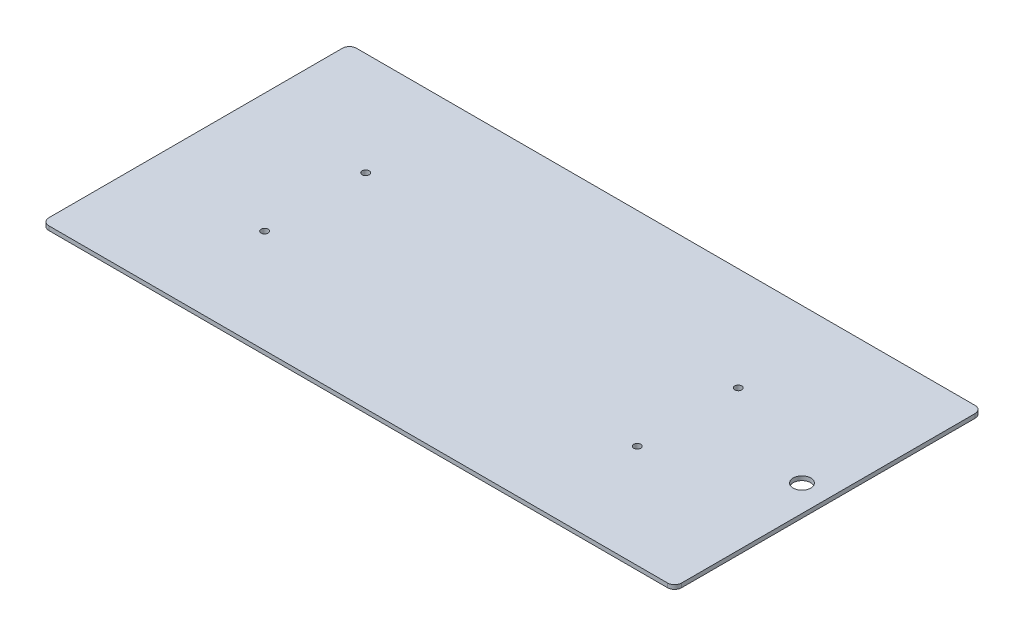
SolidWorks part; units mm, degrees
material "ABS"
ref_plane "Front Plane" through (0, 0, 0) normal (0, 0, 1) x (1, 0, 0)
ref_plane "Top Plane" through (0, 0, 0) normal (0, 1, 0) x (1, 0, 0)
ref_plane "Right Plane" through (0, 0, 0) normal (1, 0, 0) x (0, 0, -1)
sketch "Sketch1" plane through (0, 0, 0) normal (0, 1, 0) x (1, 0, 0)
  line L0 (-303.5027, 0) -> (303.5027, 0) construction
  line L1 (-223.52, -111.125) -> (223.52, -111.125)
  line L2 (-228.6, -106.045) -> (-228.6, 106.045)
  line L3 (-223.52, 111.125) -> (223.52, 111.125)
  line L4 (228.6, -106.045) -> (228.6, 106.045)
  line L5 (-228.6, -111.125) -> (228.6, 111.125) construction
  line L6 (-228.6, 111.125) -> (228.6, -111.125) construction
  line L7 (-303.5027, 36.5125) -> (303.5027, 36.5125) construction
  line L8 (-303.5027, -36.5125) -> (303.5027, -36.5125) construction
  line L9 (127, 111.125) -> (127, -111.125) construction
  line L10 (-142.24, 111.125) -> (-142.24, -111.125) construction
  arc A0 (223.52, 111.125) -> (228.6, 106.045) centre (223.52, 106.045) cw
  arc A1 (223.52, -111.125) -> (228.6, -106.045) centre (223.52, -106.045) ccw
  arc A2 (-223.52, -111.125) -> (-228.6, -106.045) centre (-223.52, -106.045) cw
  arc A3 (-228.6, 106.045) -> (-223.52, 111.125) centre (-223.52, 106.045) cw
  circle A4 centre (127, 36.5125) radius 2.54
  circle A5 centre (127, -36.5125) radius 2.54
  circle A6 centre (-142.24, 36.5125) radius 2.54
  circle A7 centre (-142.24, -36.5125) radius 2.54
  circle A8 centre (209.55, 0) radius 6.35
  point P0 (0, 0)
  point P20 (0, 0)
  point P37 (228.6, 0)
  dimension "D3" = 5.08
  dimension "D7" = 5.08
  dimension "D9" = 12.7
  dimension "D1" = 222.25
  dimension "D2" = 457.2
  dimension "D6" = 269.24
  dimension "D8" = 101.6
  dimension "D10" = 19.05
  dimension "D4" = 36.5125
  dimension "D5" = 36.5125
extrude "mainbaseplate" add sketch "Sketch1" along normal blind 3
sketch "Sketch2" plane through (0, 0, 0) normal (0, -1, 0) x (1, 0, 0)
  circle A0 centre (-142.24, 36.5125) radius 2.54 construction
  circle A1 centre (-142.24, -36.5125) radius 2.54 construction
  circle A2 centre (127, -36.5125) radius 2.54 construction
  circle A3 centre (127, 36.5125) radius 2.54 construction
  circle A4 centre (-142.24, 36.5125) radius 2.54
  circle A5 centre (-142.24, -36.5125) radius 2.54
  circle A6 centre (127, -36.5125) radius 2.54
  circle A7 centre (127, 36.5125) radius 2.54
  circle A8 centre (127, 36.5125) radius 6.096
  circle A9 centre (127, -36.5125) radius 6.096
  circle A10 centre (-142.24, -36.5125) radius 6.096
  circle A11 centre (-142.24, 36.5125) radius 6.096
  dimension "D1" = 12.192
  dimension "D2" = 5.08
extrude "BaseBoss-Extrude2" add sketch "Sketch2" along normal blind 10.16
sketch "Sketch3" [suppressed] plane through (0, 0, 0) normal (0, -1, 0) x (1, 0, 0)
  line L0 (-228.6, 0) -> (228.6, 0) construction
  line L1 (-228.6, -106.045) -> (-228.6, 106.045) construction
  line L2 (228.6, 106.045) -> (228.6, -106.045) construction
  line L3 (-228.6, 28.4) -> (-73.2, 28.4)
  line L4 (-228.6, -25.4) -> (-76.2, -25.4)
  line L6 (-228.6, 25.4) -> (-76.2, 25.4)
  line L7 (-76.2, -25.4) -> (-76.2, 25.4)
  line L8 (-228.6, -25.4) -> (-76.2, 25.4) construction
  line L9 (-228.6, 25.4) -> (-76.2, -25.4) construction
  line L10 (-73.2, -28.4) -> (-73.2, 28.4)
  line L11 (-228.6, -28.4) -> (-73.2, -28.4)
  line L12 (-228.6, 28.4) -> (-228.6, 25.4)
  line L13 (-228.6, -25.4) -> (-228.6, -28.4)
  point P6 (-152.4, 0)
  dimension "D1" = 50.8
  dimension "D2" = 152.4
  dimension "D3" = 76.2
  dimension "D4" = 3
extrude "Drive BatteryBoss-Extrude1" [suppressed] add sketch "Sketch3" along normal blind 28.575
sketch "Sketch4" [suppressed] plane through (0, -28.575, 0) normal (0, -1, 0) x (1, 0, 0)
  line L1 (-228.6, 28.4) -> (-73.2, 28.4)
  line L2 (-228.6, 28.4) -> (-228.6, -28.4)
  line L3 (-228.6, -28.4) -> (-73.2, -28.4)
  line L4 (-73.2, 28.4) -> (-73.2, -28.4)
extrude "drive Battery CapBoss-Extrude2" [suppressed] add sketch "Sketch4" along normal blind 3
sketch "Sketch5" [suppressed] plane through (0, -31.575, 0) normal (0, -1, 0) x (1, 0, 0)
  line L0 (-98.6, -28.4) -> (-73.2, -3)
  line L1 (-228.6, -28.4) -> (-73.2, -28.4) construction
  line L2 (-73.2, -28.4) -> (-73.2, 28.4) construction
  line L3 (-73.2, -3) -> (-52.1474, -3)
  line L4 (-52.1474, -3) -> (-52.1474, -43.6373)
  line L5 (-52.1474, -43.6373) -> (-98.6, -43.6373)
  line L6 (-98.6, -43.6373) -> (-98.6, -28.4)
  dimension "D1" = 25.4
  dimension "D2" = 25.4
  dimension "D3" = 21.0526
  dimension "D4" = 15.2373
extrude "Drive batterycutoutCut-Extrude1" [suppressed] cut sketch "Sketch5" against normal up to surface (31.575 mm away)
sketch "Sketch6" [suppressed] plane through (0, 3, 0) normal (0, 1, 0) x (1, 0, 0)
  line L0 (-228.6, 0) -> (228.6, 0) construction
  line L1 (-228.6, 106.045) -> (-228.6, -106.045) construction
  line L2 (228.6, -106.045) -> (228.6, 106.045) construction
  line L3 (-63.5, -41.1) -> (66.5, -41.1)
  line L4 (-63.5, -38.1) -> (63.5, -38.1)
  line L6 (-63.5, 38.1) -> (63.5, 38.1)
  line L7 (63.5, -38.1) -> (63.5, 38.1)
  line L8 (-63.5, -38.1) -> (63.5, 38.1) construction
  line L9 (-63.5, 38.1) -> (63.5, -38.1) construction
  line L10 (66.5, -41.1) -> (66.5, 41.1)
  line L11 (-63.5, 41.1) -> (66.5, 41.1)
  line L12 (-63.5, -41.1) -> (-63.5, -38.1)
  line L13 (-63.5, 38.1) -> (-63.5, 41.1)
  point P6 (0, 0)
  dimension "D1" = 127
  dimension "D2" = 76.2
  dimension "D4" = 63.5
  dimension "D3" = 3
extrude "PiBatteryBoxBoss-Extrude3" [suppressed] add sketch "Sketch6" along normal blind 25.4
sketch "Sketch7" [suppressed] plane through (0, 28.4, 0) normal (0, 1, 0) x (1, 0, 0)
  line L1 (66.5, 41.1) -> (-63.5, 41.1)
  line L2 (66.5, 41.1) -> (66.5, -41.1)
  line L3 (66.5, -41.1) -> (-63.5, -41.1)
  line L4 (-63.5, 41.1) -> (-63.5, -41.1)
extrude "PibatterytopBoss-Extrude4" [suppressed] add sketch "Sketch7" along normal blind 3
sketch "Sketch8" [suppressed] plane through (66.5, 0, 0) normal (1, 0, 0) x (0, 0, -1)
  line L0 (-38.1, 28.4) -> (38.1, 3) construction
  line L1 (38.1, 28.4) -> (-38.1, 28.4) construction
  line L2 (-31.75, 3) -> (31.75, 3)
  line L3 (-31.75, 3) -> (-31.75, 28.4)
  line L4 (-31.75, 28.4) -> (31.75, 28.4)
  line L5 (31.75, 3) -> (31.75, 28.4)
  line L6 (-31.75, 3) -> (31.75, 28.4) construction
  line L7 (-31.75, 28.4) -> (31.75, 3) construction
  point P2 (0, 15.7)
  dimension "D1" = 31.75
extrude "pibatterywiresCut-Extrude2" [suppressed] cut sketch "Sketch8" against normal blind 13.16
sketch "Sketch9" [suppressed] plane through (0, 31.4, 0) normal (0, 1, 0) x (1, 0, 0)
  line L0 (-63.5, 41.1) -> (66.5, -41.1) construction
  line L1 (-63.5, 0) -> (66.5, 0) construction
  line L2 (-5.08, -24.489) -> (52.92, -24.489) construction
  line L3 (-5.08, -24.489) -> (-5.08, 24.511) construction
  line L4 (-5.08, 24.511) -> (52.92, 24.511) construction
  line L5 (52.92, -24.489) -> (52.92, 24.511) construction
  line L6 (-5.08, -24.489) -> (52.92, 24.511) construction
  line L7 (-5.08, 24.511) -> (52.92, -24.489) construction
  line L8 (49.11, 20.701) -> (56.73, 20.701)
  line L9 (49.11, 20.701) -> (49.11, 28.321)
  line L10 (49.11, 28.321) -> (56.73, 28.321)
  line L11 (56.73, 20.701) -> (56.73, 28.321)
  line L12 (49.11, 20.701) -> (56.73, 28.321) construction
  line L13 (49.11, 28.321) -> (56.73, 20.701) construction
  line L14 (49.11, -28.299) -> (56.73, -28.299)
  line L16 (49.11, -20.679) -> (56.73, -20.679)
  line L18 (49.11, -28.299) -> (56.73, -20.679) construction
  line L19 (49.11, -20.679) -> (56.73, -28.299) construction
  line L20 (-8.89, 20.701) -> (-1.27, 20.701)
  line L21 (-8.89, 20.701) -> (-8.89, 28.321)
  line L22 (-8.89, 28.321) -> (-1.27, 28.321)
  line L23 (-1.27, 20.701) -> (-1.27, 28.321)
  line L24 (-8.89, 20.701) -> (-1.27, 28.321) construction
  line L25 (-8.89, 28.321) -> (-1.27, 20.701) construction
  line L26 (-8.89, -27.7078) -> (-1.27, -27.7078)
  line L27 (-8.89, -27.7078) -> (-8.89, -21.2702)
  line L28 (-8.89, -21.2702) -> (-1.27, -21.2702)
  line L29 (-1.27, -27.7078) -> (-1.27, -21.2702)
  line L30 (-8.89, -27.7078) -> (-1.27, -21.2702) construction
  line L31 (-8.89, -21.2702) -> (-1.27, -27.7078) construction
  line L32 (-63.5, 41.1) -> (-63.5, -41.1) construction
  line L33 (66.5, -41.1) -> (66.5, 41.1) construction
  line L34 (56.73, -20.679) -> (56.73, -28.299)
  line L35 (49.11, -20.679) -> (49.11, -28.299)
  circle A0 centre (52.92, 24.511) radius 1.35
  circle A1 centre (-5.08, 24.511) radius 1.35
  circle A2 centre (-5.08, -24.489) radius 1.35
  circle A3 centre (52.92, -24.489) radius 1.35
  point P4 (-8.057, 0)
  dimension "D3" = 2.7
  dimension "D4" = 7.62
  dimension "D1" = 58
  dimension "D2" = 49
  dimension "D5" = 7.62
  dimension "D6" = 7.62
  dimension "D7" = 7.62
  dimension "D8" = 7.62
  dimension "D9" = 7.62
  dimension "D10" = 58.42
  dimension "D11" = 24.511
  dimension "D12" = 7.62
extrude "PiBoardBoss-Extrude5" [suppressed] add sketch "Sketch9" along normal blind 3
sketch "Sketch10" [suppressed] plane through (0, 3, 0) normal (0, 1, 0) x (1, 0, 0)
  line L0 (228.6, 0) -> (-228.6, 0) construction
  line L1 (228.6, -106.045) -> (228.6, 106.045) construction
  line L2 (-228.6, 106.045) -> (-228.6, -106.045) construction
  line L3 (104.95, 18.875) -> (174.45, 18.875)
  line L4 (107.95, -15.875) -> (171.45, -15.875)
  line L5 (107.95, -15.875) -> (107.95, -6.175)
  line L6 (107.95, 15.875) -> (171.45, 15.875)
  line L7 (171.45, -15.875) -> (171.45, 15.875)
  line L8 (107.95, -15.875) -> (171.45, 15.875) construction
  line L9 (107.95, 15.875) -> (171.45, -15.875) construction
  line L10 (174.45, -18.875) -> (174.45, 18.875)
  line L11 (104.95, -18.875) -> (174.45, -18.875)
  line L12 (104.95, -18.875) -> (104.95, -6.175)
  line L13 (104.95, 6.175) -> (107.95, 6.175)
  line L14 (104.95, -6.175) -> (107.95, -6.175)
  line L15 (104.95, 6.175) -> (104.95, 18.875)
  line L16 (104.95, -18.875) -> (104.95, 18.875) construction
  line L17 (107.95, 6.175) -> (107.95, 15.875)
  line L18 (107.95, -15.875) -> (107.95, 15.875) construction
  point P6 (139.7, 0)
  dimension "D1" = 31.75
  dimension "D2" = 63.5
  dimension "D3" = 139.7
  dimension "D5" = 12.7
  dimension "D6" = 12.7
  dimension "D4" = 3
extrude "PanTilt-Extrude6" [suppressed] add sketch "Sketch10" along normal blind 53.34
sketch "Sketch11" [suppressed] plane through (0, 56.34, 0) normal (0, 1, 0) x (1, 0, 0)
  line L1 (104.95, 18.875) -> (174.45, 18.875)
  line L2 (104.95, 18.875) -> (104.95, -18.875)
  line L3 (104.95, -18.875) -> (174.45, -18.875)
  line L4 (174.45, 18.875) -> (174.45, -18.875)
extrude "Boss-Extrude7" [suppressed] add sketch "Sketch11" along normal blind 3
sketch "Sketch12" [suppressed] plane through (0, 59.34, 0) normal (0, 1, 0) x (1, 0, 0)
  line L0 (104.95, 0) -> (174.45, 0) construction
  line L1 (104.95, 18.875) -> (104.95, -18.875) construction
  line L2 (174.45, -18.875) -> (174.45, 18.875) construction
  line L3 (118.745, 1.9377) -> (104.95, 1.9377)
  line L4 (118.745, -10.795) -> (160.655, -10.795)
  line L5 (118.745, -10.795) -> (118.745, -1.9901)
  line L6 (118.745, 10.795) -> (160.655, 10.795)
  line L7 (160.655, -10.795) -> (160.655, 10.795)
  line L8 (118.745, -10.795) -> (160.655, 10.795) construction
  line L9 (118.745, 10.795) -> (160.655, -10.795) construction
  line L10 (115.57, -5.08) -> (163.83, -5.08) construction
  line L11 (115.57, -5.08) -> (115.57, 5.08) construction
  line L12 (115.57, 5.08) -> (163.83, 5.08) construction
  line L13 (163.83, -5.08) -> (163.83, 5.08) construction
  line L14 (115.57, -5.08) -> (163.83, 5.08) construction
  line L15 (115.57, 5.08) -> (163.83, -5.08) construction
  line L16 (118.745, -1.9901) -> (104.95, -1.9901)
  line L17 (118.745, 1.9377) -> (118.745, 10.795)
  line L18 (104.95, 1.9377) -> (95.8416, 0)
  line L19 (95.8416, 0) -> (104.95, -1.9901)
  circle A0 centre (163.83, 5.08) radius 2.0193
  circle A1 centre (163.83, -5.08) radius 2.0193
  circle A2 centre (115.57, 5.08) radius 2.0193
  circle A3 centre (115.57, -5.08) radius 2.0193
  point P6 (139.7, 0)
  point P11 (139.7, 0)
  dimension "D5" = 4.0386
  dimension "D1" = 21.59
  dimension "D2" = 41.91
  dimension "D3" = 48.26
  dimension "D4" = 10.16
  dimension "D6" = 1.9377
  dimension "D7" = 1.9901
extrude "Cut-Extrude3" [suppressed] cut sketch "Sketch12" against normal up to surface (56.34 mm away)
sketch "Sketch13" [suppressed] plane through (0, 3, 0) normal (0, 1, 0) x (1, 0, 0)
  line L0 (228.6, 0) -> (-228.6, 0) construction
  line L1 (228.6, -106.045) -> (228.6, 106.045) construction
  line L2 (-228.6, 106.045) -> (-228.6, -106.045) construction
  line L3 (198.12, 0) -> (198.12, 25.4)
  line L4 (198.12, 25.4) -> (172.72, 69.3941)
  line L5 (172.72, 69.3941) -> (136.799, 105.3151)
  line L6 (198.12, 25.4) -> (198.12, 129.9736) construction
  line L7 (172.72, 69.3941) -> (172.72, 97.5573) construction
  line L8 (136.799, 105.3151) -> (-185.781, 105.3151)
  line L9 (-185.781, 105.3151) -> (-221.702, 69.3941)
  line L10 (-221.702, 69.3941) -> (-221.702, 0)
  line L11 (-185.781, 105.3151) -> (-290.6809, 105.3151) construction
  line L12 (195.12, 0) -> (195.12, 24.5962)
  line L13 (195.12, 24.5962) -> (170.3194, 67.552)
  line L14 (170.3194, 67.552) -> (135.5563, 102.3151)
  line L15 (135.5563, 102.3151) -> (-184.5384, 102.3151)
  line L16 (-184.5384, 102.3151) -> (-218.702, 68.1514)
  line L17 (-218.702, 68.1514) -> (-218.702, 0)
  line L18 (172.72, -69.3941) -> (172.72, -97.5573) construction
  line L19 (198.12, -25.4) -> (198.12, -129.9736) construction
  line L20 (-218.702, -68.1514) -> (-218.702, 0)
  line L21 (-184.5384, -102.3151) -> (-218.702, -68.1514)
  line L22 (135.5563, -102.3151) -> (-184.5384, -102.3151)
  line L23 (170.3194, -67.552) -> (135.5563, -102.3151)
  line L24 (195.12, -24.5962) -> (170.3194, -67.552)
  line L25 (195.12, 0) -> (195.12, -24.5962)
  line L26 (-221.702, -69.3941) -> (-221.702, 0)
  line L27 (-185.781, -105.3151) -> (-221.702, -69.3941)
  line L28 (136.799, -105.3151) -> (-185.781, -105.3151)
  line L29 (172.72, -69.3941) -> (136.799, -105.3151)
  line L30 (198.12, -25.4) -> (172.72, -69.3941)
  line L31 (198.12, 0) -> (198.12, -25.4)
  dimension "D1" = 30.48
  dimension "D2" = 25.4
  dimension "D3" = 30
  dimension "D4" = 50.8
  dimension "D5" = 45
  dimension "D6" = 50.8
  dimension "D7" = 322.58
  dimension "D8" = 50.8
  dimension "D9" = 45
  dimension "D10" = 3
extrude "Bottom Shell WallsBoss-Extrude8" [suppressed] add sketch "Sketch13" along normal blind 68.58
sketch "Sketch14" [suppressed] plane through (121.057, 0, -121.057) normal (0.7071, 0, -0.7071) x (-0.7071, 0, -0.7071)
  line L0 (-47.6625, 71.58) -> (-47.6625, 3) construction
  line L1 (-73.0625, 71.58) -> (-22.2625, 71.58) construction
  line L2 (-73.0625, 3) -> (-22.2625, 3) construction
  line L3 (-47.6625, 37.29) -> (-25.0131, 37.29) construction
  circle A0 centre (-47.6625, 64.722) radius 1.3526
  circle A1 centre (-47.6625, 9.858) radius 1.3526
  circle A2 centre (-29.8825, 37.29) radius 4.7625
  point P10 (-47.6625, 37.29)
  dimension "D1" = 2.7051
  dimension "D4" = 9.525
  dimension "D2" = 54.864
  dimension "D3" = 27.432
  dimension "D5" = 17.78
extrude "Sharp1Cut-Extrude4" [suppressed] cut sketch "Sketch14" against normal blind 12.7
sketch "Sketch15" [suppressed] plane through (159.5885, 0, -92.1385) normal (0.866, 0, -0.5) x (-0.5, 0, -0.866)
  line L0 (-51.663, 71.58) -> (-51.663, 3) construction
  line L1 (-77.063, 71.58) -> (-26.263, 71.58) construction
  line L2 (-77.063, 3) -> (-26.263, 3) construction
  line L3 (-51.663, 37.29) -> (-29.7061, 37.29) construction
  circle A0 centre (-51.663, 64.722) radius 1.3526
  circle A1 centre (-51.663, 9.858) radius 1.3526
  circle A2 centre (-33.883, 37.29) radius 4.7625
  point P10 (-51.663, 37.29)
  dimension "D1" = 2.7051
  dimension "D4" = 9.525
  dimension "D2" = 27.432
  dimension "D3" = 54.864
  dimension "D5" = 17.78
extrude "Sharp2Cut-Extrude5" [suppressed] cut sketch "Sketch15" against normal blind 7.62
sketch "Sketch16" [suppressed] plane through (198.12, 0, 0) normal (1, 0, 0) x (0, 0, -1)
  line L0 (0, 71.58) -> (0, 3) construction
  line L1 (-25.4, 71.58) -> (25.4, 71.58) construction
  line L2 (-25.4, 3) -> (25.4, 3) construction
  line L3 (0, 37.29) -> (21.2381, 37.29) construction
  circle A0 centre (0, 64.722) radius 1.3526
  circle A1 centre (0, 9.858) radius 1.3525
  circle A2 centre (17.78, 37.29) radius 4.7625
  dimension "D1" = 2.7051
  dimension "D4" = 9.525
  dimension "D2" = 27.432
  dimension "D3" = 54.864
  dimension "D5" = 17.78
extrude "Sharp3Cut-Extrude6" [suppressed] cut sketch "Sketch16" against normal blind 7.62
sketch "Sketch17" [suppressed] plane through (159.5885, 0, 92.1385) normal (0.866, 0, 0.5) x (0.5, 0, -0.866)
  line L0 (51.663, 71.58) -> (51.663, 3) construction
  line L1 (26.263, 71.58) -> (77.063, 71.58) construction
  line L2 (26.263, 3) -> (77.063, 3) construction
  line L3 (51.663, 37.29) -> (70.4023, 37.29) construction
  circle A0 centre (51.663, 64.722) radius 1.3526
  circle A1 centre (51.663, 9.858) radius 1.3526
  circle A2 centre (69.443, 37.29) radius 4.7625
  dimension "D1" = 2.7051
  dimension "D2" = 2.7051
  dimension "D3" = 9.525
  dimension "D4" = 17.78
  dimension "D5" = 27.432
  dimension "D6" = 54.864
extrude "SharpCut-Extrude7" [suppressed] cut sketch "Sketch17" against normal blind 7.62
sketch "Sketch18" [suppressed] plane through (121.057, 0, 121.057) normal (0.7071, 0, 0.7071) x (0.7071, 0, -0.7071)
  line L0 (47.6625, 71.58) -> (47.6625, 3) construction
  line L1 (22.2625, 71.58) -> (73.0625, 71.58) construction
  line L2 (22.2625, 3) -> (73.0625, 3) construction
  line L3 (25.604, 37.29) -> (69.7209, 37.29) construction
  circle A0 centre (47.6625, 64.722) radius 1.3526
  circle A1 centre (47.6625, 9.858) radius 1.3526
  circle A2 centre (65.4425, 37.29) radius 4.7625
  point P13 (47.6625, 37.29)
  dimension "D1" = 9.525
  dimension "D3" = 2.7051
  dimension "D4" = 2.7051
  dimension "D2" = 17.78
  dimension "D5" = 27.432
  dimension "D6" = 54.864
extrude "SharpCut-Extrude8" [suppressed] cut sketch "Sketch18" against normal blind 7.62
sketch "Sketch19" [suppressed] plane through (0, 71.58, 0) normal (0, 1, 0) x (1, 0, 0)
  line L0 (-223.52, -111.125) -> (223.52, -111.125) construction
  line L1 (228.6, -106.045) -> (228.6, 106.045) construction
  line L2 (223.52, 111.125) -> (-223.52, 111.125) construction
  line L3 (104.95, -111.125) -> (223.52, -111.125)
  line L4 (228.6, -106.045) -> (228.6, 106.045)
  line L5 (223.52, 111.125) -> (104.95, 111.125)
  line L6 (104.95, 111.125) -> (104.95, -111.125)
  arc A0 (223.52, -111.125) -> (228.6, -106.045) centre (223.52, -106.045) ccw construction
  arc A1 (228.6, 106.045) -> (223.52, 111.125) centre (223.52, 106.045) ccw construction
  arc A2 (223.52, -111.125) -> (228.6, -106.045) centre (223.52, -106.045) ccw
  arc A3 (228.6, 106.045) -> (223.52, 111.125) centre (223.52, 106.045) ccw
extrude "TopSensorplateBoss-Extrude8" [suppressed] add sketch "Sketch19" along normal blind 3
sketch "Sketch21" [suppressed] plane through (0, 74.58, 0) normal (0, 1, 0) x (1, 0, 0)
  line L0 (104.95, -18.875) -> (174.45, -18.875) construction
  line L1 (174.45, -18.875) -> (174.45, 18.875) construction
  line L2 (174.45, 18.875) -> (104.95, 18.875) construction
  line L3 (104.95, -18.875) -> (164.29, -18.875)
  line L4 (174.45, -8.715) -> (174.45, 8.715)
  line L5 (164.29, 18.875) -> (104.95, 18.875)
  line L6 (104.95, 18.875) -> (84.8462, 2.2825)
  line L7 (84.8462, 2.2825) -> (104.95, -18.875)
  arc A0 (164.29, -18.875) -> (174.45, -8.715) centre (164.29, -8.715) ccw
  arc A1 (174.45, 8.715) -> (164.29, 18.875) centre (164.29, 8.715) ccw
  circle A2 centre (127, -36.5125) radius 6.096 construction
  circle A3 centre (127, 36.5125) radius 6.096 construction
  circle A4 centre (127, -36.5125) radius 6.096
  circle A5 centre (127, 36.5125) radius 6.096
  dimension "D1" = 10.16
extrude "topsensorplateCut-Extrude4" [suppressed] cut sketch "Sketch21" against normal blind 8.08
sketch "Sketch22" [suppressed] plane through (0, 0, 0) normal (0, -1, 0) x (1, 0, 0)
  line L0 (228.6, 0) -> (-228.6, 0) construction
  line L1 (228.6, 106.045) -> (228.6, -106.045) construction
  line L2 (-228.6, 28.4) -> (-228.6, -28.4) construction
  line L3 (220.98, 0) -> (220.98, 76.2)
  line L4 (220.98, 76.2) -> (193.675, 103.505)
  line L5 (193.675, 103.505) -> (-25.4, 103.505)
  line L6 (-223.52, 111.125) -> (223.52, 111.125) construction
  line L7 (217.98, 0) -> (217.98, 74.9574)
  line L8 (217.98, 74.9574) -> (192.4324, 100.505)
  line L9 (192.4324, 100.505) -> (-25.4, 100.505)
  line L10 (-25.4, 103.505) -> (-25.4, 100.505)
  line L11 (217.98, 0) -> (217.98, -74.9574)
  line L12 (220.98, 0) -> (220.98, -76.2)
  line L13 (-25.4, -103.505) -> (-25.4, -100.505)
  line L14 (192.4324, -100.505) -> (-25.4, -100.505)
  line L15 (217.98, -74.9574) -> (192.4324, -100.505)
  line L16 (193.675, -103.505) -> (-25.4, -103.505)
  line L17 (220.98, -76.2) -> (193.675, -103.505)
  line L18 (-220.98, 28.4) -> (-220.98, 76.2)
  line L19 (-73.2, 28.4) -> (-228.6, 28.4) construction
  line L20 (-220.98, 76.2) -> (-193.548, 103.505)
  line L21 (-193.548, 103.505) -> (-127, 103.505)
  line L22 (-228.6, 28.4) -> (-228.6, 106.045) construction
  line L23 (-217.98, 28.4) -> (-217.98, 74.9533)
  line L24 (-217.98, 74.9533) -> (-192.3094, 100.505)
  line L25 (-192.3094, 100.505) -> (-127, 100.505)
  line L26 (-127, 103.505) -> (-127, 100.505)
  line L27 (-220.98, 28.4) -> (-217.98, 28.4)
  line L28 (-127, -103.505) -> (-127, -100.505)
  line L29 (-192.3094, -100.505) -> (-127, -100.505)
  line L30 (-217.98, -74.9533) -> (-192.3094, -100.505)
  line L31 (-217.98, -28.4) -> (-217.98, -74.9533)
  line L32 (-193.548, -103.505) -> (-127, -103.505)
  line L33 (-220.98, -76.2) -> (-193.548, -103.505)
  line L34 (-220.98, -28.4) -> (-220.98, -76.2)
  line L35 (-220.98, -28.4) -> (-217.98, -28.4)
  dimension "D1" = 7.62
  dimension "D2" = 7.62
  dimension "D3" = 76.2
  dimension "D4" = 34.925
  dimension "D5" = 254
  dimension "D7" = 7.62
  dimension "D8" = 76.2
  dimension "D9" = 7.62
  dimension "D10" = 101.6
  dimension "D11" = 35.052
  dimension "D6" = 3
  dimension "D12" = 3
extrude "frontrockerpanBoss-Extrude9" [suppressed] add sketch "Sketch22" along normal blind 45.72
sketch "Sketch23" [suppressed] plane through (0, 0, -103.505) normal (0, 0, -1) x (-1, 0, 0)
  line L0 (25.4, 0) -> (-193.675, 0) construction
  line L2 (-223.1134, -81.0052) -> (22.7571, -81.0052) construction
  line L3 (22.7571, -81.0052) -> (254.0819, -81.0052) construction
  circle A1 centre (-127, -81.0052) radius 63.5
  circle A2 centre (152.4, -81.0052) radius 63.5
  dimension "D1" = 81.0052
  dimension "D4" = 127
  dimension "D2" = 22.7571
  dimension "D3" = 223.1134
  dimension "D5" = 127
  dimension "D6" = 279.4
extrude "TireCut-Extrude5" [suppressed] cut sketch "Sketch23" against normal blind 25.4
sketch "Sketch24" [suppressed] plane through (-221.702, 0, 0) normal (-1, 0, 0) x (0, 0, 1)
  line L0 (-69.3941, 71.58) -> (69.3941, 3) construction
  circle A0 centre (0, 37.29) radius 10.9855
  dimension "D1" = 21.971
extrude "Cut-Extrude6" [suppressed] cut sketch "Sketch24" against normal blind 7.62
sketch "Sketch25" [suppressed] plane through (0, 71.58, 0) normal (0, 1, 0) x (1, 0, 0)
  line L3 (-223.52, -111.125) -> (223.52, -111.125) construction
  line L5 (-228.6, 106.045) -> (-228.6, -106.045) construction
  line L6 (223.52, 111.125) -> (-223.52, 111.125) construction
  line L7 (-223.52, -111.125) -> (-147.32, -111.125)
  line L8 (-228.6, 106.045) -> (-228.6, -106.045)
  line L9 (-147.32, 111.125) -> (-223.52, 111.125)
  line L10 (-147.32, 111.125) -> (-147.32, -111.125)
  arc A2 (-228.6, -106.045) -> (-223.52, -111.125) centre (-223.52, -106.045) ccw construction
  arc A3 (-223.52, 111.125) -> (-228.6, 106.045) centre (-223.52, 106.045) ccw construction
  arc A4 (-228.6, -106.045) -> (-223.52, -111.125) centre (-223.52, -106.045) ccw
  arc A5 (-223.52, 111.125) -> (-228.6, 106.045) centre (-223.52, 106.045) ccw
  dimension "D1" = 147.32
extrude "ReartopdeckBoss-Extrude10" [suppressed] add sketch "Sketch25" along normal blind 3
sketch "Sketch28" [suppressed] plane through (0, 0, 103.505) normal (0, 0, 1) x (1, 0, 0)
  line L0 (-205.194, -45.72) -> (-93.1399, -108.4782)
  line L1 (-93.1399, -108.4782) -> (179.794, -45.72)
  line L2 (74.206, -45.72) -> (-102.0458, -69.7467)
  line L3 (-102.0458, -69.7467) -> (-127, -22.8065)
  arc A0 (-192.3094, -31.6141) -> (-205.194, -45.72) centre (-152.4, -81.0052) ccw construction
  arc A1 (-127, -22.8065) -> (-192.3094, -31.6141) centre (-152.4, -81.0052) ccw construction
  arc A2 (179.794, -45.72) -> (74.206, -45.72) centre (127, -81.0052) ccw construction
  arc A3 (-192.3094, -31.6141) -> (-205.194, -45.72) centre (-152.4, -81.0052) ccw
  arc A4 (-127, -22.8065) -> (-192.3094, -31.6141) centre (-152.4, -81.0052) ccw
  arc A5 (179.794, -45.72) -> (74.206, -45.72) centre (127, -81.0052) ccw
extrude "TireCut-Extrude8" [suppressed] cut sketch "Sketch28" against normal blind 35.56
sketch "Sketch30" [suppressed] plane through (0, 74.58, 0) normal (0, 1, 0) x (1, 0, 0)
  line L0 (-147.32, 0) -> (-228.6, 0) construction
  line L1 (-147.32, -111.125) -> (-147.32, 111.125) construction
  line L2 (-228.6, 106.045) -> (-228.6, -106.045) construction
  circle A0 centre (-166.37, 0) radius 6.35
  dimension "D1" = 12.7
  dimension "D2" = 19.05
extrude "Cut-Extrude10" [suppressed] cut sketch "Sketch30" against normal blind 11.684
sketch "Sketch31" [suppressed] plane through (0, 0, 0) normal (1, 0, 0) x (0, 0, -1)
  line L0 (102.3151, 71.58) -> (102.3151, 3) construction
  line L1 (-102.3151, 71.58) -> (-76.9151, 71.58)
  line L2 (-102.3151, 71.58) -> (-102.3151, 68.58)
  line L3 (-102.3151, 68.58) -> (-76.9151, 68.58)
  line L4 (102.3151, 71.58) -> (102.3151, 68.58)
  line L5 (-76.9151, 71.58) -> (-76.9151, 68.58)
  line L6 (76.9151, 71.58) -> (76.9151, 68.58)
  line L7 (76.9151, 71.58) -> (102.3151, 71.58)
  line L8 (76.9151, 68.58) -> (102.3151, 68.58)
  dimension "D1" = 3
  dimension "D2" = 25.4
  dimension "D3" = 25.4
extrude "Boss-Extrude8" [suppressed] add sketch "Sketch31" along normal blind 134.62 and the other way blind 180.34
